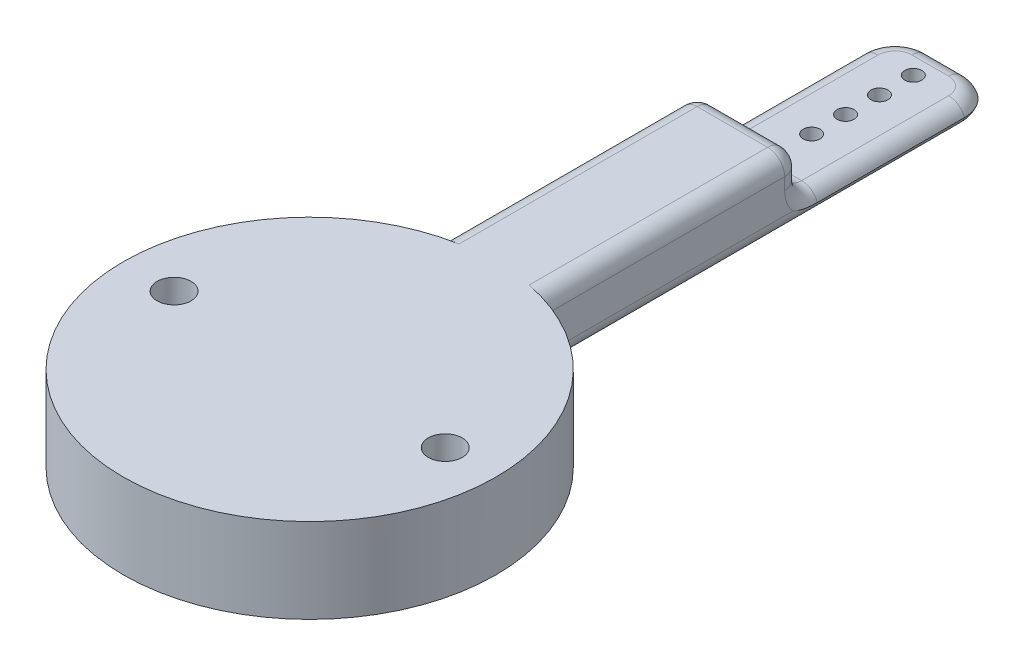
SolidWorks part; units mm, degrees
ref_plane "前视基准面" through (0, 0, 0) normal (0, 0, 1) x (1, 0, 0)
ref_plane "上视基准面" through (0, 0, 0) normal (0, 1, 0) x (1, 0, 0)
ref_plane "右视基准面" through (0, 0, 0) normal (1, 0, 0) x (0, 0, -1)
sketch "草图1" plane through (0, 0, 0) normal (0, 1, 0) x (1, 0, 0)
  circle A0 centre (0, 0) radius 15
  dimension "D1" = 30
extrude "凸台-拉伸3" add sketch "草图1" along normal blind 6
sketch "草图2" plane through (0, 0, 0) normal (0, -1, 0) x (1, 0, 0)
  circle A0 centre (0, 0) radius 10
  dimension "D1" = 20
extrude "切除-拉伸1" cut sketch "草图2" against normal blind 2
sketch "草图3" plane through (0, 2, 0) normal (0, -1, 0) x (1, 0, 0)
  line L0 (-19.2837, 0) -> (17.324, 0) construction
  line L1 (-8, 0) -> (8, 0) construction
  circle A0 centre (8, 0) radius 1
  circle A1 centre (-8, 0) radius 1
  dimension "D3" = 2
  dimension "D4" = 2
  dimension "D1" = 8
  dimension "D2" = 16
extrude "切除-拉伸2" cut sketch "草图3" against normal blind 32
sketch "草图4" plane through (0, 2, 0) normal (0, -1, 0) x (1, 0, 0)
  circle A0 centre (0, 0) radius 4
  dimension "D1" = 8
extrude "切除-拉伸3" cut sketch "草图4" against normal blind 2
sketch "草图5" plane through (0, 6, 0) normal (0, 1, 0) x (1, 0, 0)
  line L0 (0, 0) -> (0, 31.4873) construction
  line L1 (1.8873, 14.6141) -> (3.8489, 14.2239)
  line L4 (-1, 14.7015) -> (1, 14.7015)
  line L6 (4.7021, 13.9651) -> (6.5499, 13.1997)
  line L7 (7.3362, 12.7794) -> (8.9992, 11.6683)
  line L8 (9.6884, 11.1026) -> (11.1026, 9.6884)
  line L9 (11.6683, 8.9992) -> (12.7794, 7.3362)
  line L10 (13.1997, 6.5499) -> (13.9651, 4.7021)
  line L11 (14.2239, 3.8489) -> (14.6141, 1.8873)
  line L12 (14.7015, 1) -> (14.7015, -1)
  line L13 (14.6141, -1.8873) -> (14.2239, -3.8489)
  line L14 (13.9651, -4.7021) -> (13.1997, -6.5499)
  line L15 (12.7794, -7.3362) -> (11.6683, -8.9992)
  line L16 (11.1026, -9.6884) -> (9.6884, -11.1026)
  line L17 (8.9992, -11.6683) -> (7.3362, -12.7794)
  line L18 (6.5499, -13.1997) -> (4.7021, -13.9651)
  line L19 (3.8489, -14.2239) -> (1.8873, -14.6141)
  line L20 (1, -14.7015) -> (-1, -14.7015)
  line L21 (-1.8873, -14.6141) -> (-3.8489, -14.2239)
  line L22 (-4.7021, -13.9651) -> (-6.5499, -13.1997)
  line L23 (-7.3362, -12.7794) -> (-8.9992, -11.6683)
  line L24 (-9.6884, -11.1026) -> (-11.1026, -9.6884)
  line L25 (-11.6683, -8.9992) -> (-12.7794, -7.3362)
  line L26 (-13.1997, -6.5499) -> (-13.9651, -4.7021)
  line L27 (-14.2239, -3.8489) -> (-14.6141, -1.8873)
  line L28 (-14.7015, -1) -> (-14.7015, 1)
  line L29 (-14.6141, 1.8873) -> (-14.2239, 3.8489)
  line L30 (-13.9651, 4.7021) -> (-13.1997, 6.5499)
  line L31 (-12.7794, 7.3362) -> (-11.6683, 8.9992)
  line L32 (-11.1026, 9.6884) -> (-9.6884, 11.1026)
  line L33 (-8.9992, 11.6683) -> (-7.3362, 12.7794)
  line L34 (-6.5499, 13.1997) -> (-4.7021, 13.9651)
  line L35 (-3.8489, 14.2239) -> (-1.8873, 14.6141)
  spline S0 degree 2 poles (0, 17.0015) (-0.7779, 15.9692) (-1, 14.7015) knots 0 0 0 1 1 1
  spline S1 degree 2 poles (0, 17.0015) (0.7445, 15.9556) (1, 14.7015) knots 0 0 0 1 1 1
  spline S2 degree 2 poles (3.3168, 16.6748) (2.3525, 15.8141) (1.8873, 14.6141) knots 0 0 0 1 1 1
  spline S3 degree 2 poles (3.3168, 16.6748) (3.843, 15.5038) (3.8489, 14.2239) knots 0 0 0 1 1 1
  spline S4 degree 2 poles (6.5062, 15.7073) (5.3925, 15.0513) (4.7021, 13.9651) knots 0 0 0 1 1 1
  spline S5 degree 2 poles (6.5062, 15.7073) (6.7938, 14.4561) (6.5499, 13.1997) knots 0 0 0 1 1 1
  spline S6 degree 2 poles (9.4455, 14.1362) (8.2252, 13.7101) (7.3362, 12.7794) knots 0 0 0 1 1 1
  spline S7 degree 2 poles (9.4455, 14.1362) (9.4835, 12.8529) (8.9992, 11.6683) knots 0 0 0 1 1 1
  spline S8 degree 2 poles (12.0219, 12.0219) (10.7419, 11.842) (9.6884, 11.1026) knots 0 0 0 1 1 1
  spline S9 degree 2 poles (12.0219, 12.0219) (11.8088, 10.7558) (11.1026, 9.6884) knots 0 0 0 1 1 1
  spline S10 degree 2 poles (14.1362, 9.4455) (12.8457, 9.5188) (11.6683, 8.9992) knots 0 0 0 1 1 1
  spline S11 degree 2 poles (14.1362, 9.4455) (13.6802, 8.2454) (12.7794, 7.3362) knots 0 0 0 1 1 1
  spline S12 degree 2 poles (15.7073, 6.5062) (14.456, 6.8299) (13.1997, 6.5499) knots 0 0 0 1 1 1
  spline S13 degree 2 poles (15.7073, 6.5062) (15.026, 5.4181) (13.9651, 4.7021) knots 0 0 0 1 1 1
  spline S14 degree 2 poles (16.6748, 3.3168) (15.5106, 3.8784) (14.2239, 3.8489) knots 0 0 0 1 1 1
  spline S15 degree 2 poles (16.6748, 3.3168) (15.7943, 2.3826) (14.6141, 1.8873) knots 0 0 0 1 1 1
  spline S16 degree 2 poles (17.0015, 0) (15.9692, 0.7779) (14.7015, 1) knots 0 0 0 1 1 1
  spline S17 degree 2 poles (17.0015, 0) (15.9556, -0.7445) (14.7015, -1) knots 0 0 0 1 1 1
  spline S18 degree 2 poles (16.6748, -3.3168) (15.8141, -2.3525) (14.6141, -1.8873) knots 0 0 0 1 1 1
  spline S19 degree 2 poles (16.6748, -3.3168) (15.5038, -3.843) (14.2239, -3.8489) knots 0 0 0 1 1 1
  spline S20 degree 2 poles (15.7073, -6.5062) (15.0513, -5.3925) (13.9651, -4.7021) knots 0 0 0 1 1 1
  spline S21 degree 2 poles (15.7073, -6.5062) (14.4561, -6.7938) (13.1997, -6.5499) knots 0 0 0 1 1 1
  spline S22 degree 2 poles (14.1362, -9.4455) (13.7101, -8.2252) (12.7794, -7.3362) knots 0 0 0 1 1 1
  spline S23 degree 2 poles (14.1362, -9.4455) (12.8529, -9.4835) (11.6683, -8.9992) knots 0 0 0 1 1 1
  spline S24 degree 2 poles (12.0219, -12.0219) (11.842, -10.7419) (11.1026, -9.6884) knots 0 0 0 1 1 1
  spline S25 degree 2 poles (12.0219, -12.0219) (10.7558, -11.8088) (9.6884, -11.1026) knots 0 0 0 1 1 1
  spline S26 degree 2 poles (9.4455, -14.1362) (9.5188, -12.8457) (8.9992, -11.6683) knots 0 0 0 1 1 1
  spline S27 degree 2 poles (9.4455, -14.1362) (8.2454, -13.6802) (7.3362, -12.7794) knots 0 0 0 1 1 1
  spline S28 degree 2 poles (6.5062, -15.7073) (6.8299, -14.456) (6.5499, -13.1997) knots 0 0 0 1 1 1
  spline S29 degree 2 poles (6.5062, -15.7073) (5.4181, -15.026) (4.7021, -13.9651) knots 0 0 0 1 1 1
  spline S30 degree 2 poles (3.3168, -16.6748) (3.8784, -15.5106) (3.8489, -14.2239) knots 0 0 0 1 1 1
  spline S31 degree 2 poles (3.3168, -16.6748) (2.3826, -15.7943) (1.8873, -14.6141) knots 0 0 0 1 1 1
  spline S32 degree 2 poles (0, -17.0015) (0.7779, -15.9692) (1, -14.7015) knots 0 0 0 1 1 1
  spline S33 degree 2 poles (0, -17.0015) (-0.7445, -15.9556) (-1, -14.7015) knots 0 0 0 1 1 1
  spline S34 degree 2 poles (-3.3168, -16.6748) (-2.3525, -15.8141) (-1.8873, -14.6141) knots 0 0 0 1 1 1
  spline S35 degree 2 poles (-3.3168, -16.6748) (-3.843, -15.5038) (-3.8489, -14.2239) knots 0 0 0 1 1 1
  spline S36 degree 2 poles (-6.5062, -15.7073) (-5.3925, -15.0513) (-4.7021, -13.9651) knots 0 0 0 1 1 1
  spline S37 degree 2 poles (-6.5062, -15.7073) (-6.7938, -14.4561) (-6.5499, -13.1997) knots 0 0 0 1 1 1
  spline S38 degree 2 poles (-9.4455, -14.1362) (-8.2252, -13.7101) (-7.3362, -12.7794) knots 0 0 0 1 1 1
  spline S39 degree 2 poles (-9.4455, -14.1362) (-9.4835, -12.8529) (-8.9992, -11.6683) knots 0 0 0 1 1 1
  spline S40 degree 2 poles (-12.0219, -12.0219) (-10.7419, -11.842) (-9.6884, -11.1026) knots 0 0 0 1 1 1
  spline S41 degree 2 poles (-12.0219, -12.0219) (-11.8088, -10.7558) (-11.1026, -9.6884) knots 0 0 0 1 1 1
  spline S42 degree 2 poles (-14.1362, -9.4455) (-12.8457, -9.5188) (-11.6683, -8.9992) knots 0 0 0 1 1 1
  spline S43 degree 2 poles (-14.1362, -9.4455) (-13.6802, -8.2454) (-12.7794, -7.3362) knots 0 0 0 1 1 1
  spline S44 degree 2 poles (-15.7073, -6.5062) (-14.456, -6.8299) (-13.1997, -6.5499) knots 0 0 0 1 1 1
  spline S45 degree 2 poles (-15.7073, -6.5062) (-15.026, -5.4181) (-13.9651, -4.7021) knots 0 0 0 1 1 1
  spline S46 degree 2 poles (-16.6748, -3.3168) (-15.5106, -3.8784) (-14.2239, -3.8489) knots 0 0 0 1 1 1
  spline S47 degree 2 poles (-16.6748, -3.3168) (-15.7943, -2.3826) (-14.6141, -1.8873) knots 0 0 0 1 1 1
  spline S48 degree 2 poles (-17.0015, 0) (-15.9692, -0.7779) (-14.7015, -1) knots 0 0 0 1 1 1
  spline S49 degree 2 poles (-17.0015, 0) (-15.9556, 0.7445) (-14.7015, 1) knots 0 0 0 1 1 1
  spline S50 degree 2 poles (-16.6748, 3.3168) (-15.8141, 2.3525) (-14.6141, 1.8873) knots 0 0 0 1 1 1
  spline S51 degree 2 poles (-16.6748, 3.3168) (-15.5038, 3.843) (-14.2239, 3.8489) knots 0 0 0 1 1 1
  spline S52 degree 2 poles (-15.7073, 6.5062) (-15.0513, 5.3925) (-13.9651, 4.7021) knots 0 0 0 1 1 1
  spline S53 degree 2 poles (-15.7073, 6.5062) (-14.4561, 6.7938) (-13.1997, 6.5499) knots 0 0 0 1 1 1
  spline S54 degree 2 poles (-14.1362, 9.4455) (-13.7101, 8.2252) (-12.7794, 7.3362) knots 0 0 0 1 1 1
  spline S55 degree 2 poles (-14.1362, 9.4455) (-12.8529, 9.4835) (-11.6683, 8.9992) knots 0 0 0 1 1 1
  spline S56 degree 2 poles (-12.0219, 12.0219) (-11.842, 10.7419) (-11.1026, 9.6884) knots 0 0 0 1 1 1
  spline S57 degree 2 poles (-12.0219, 12.0219) (-10.7558, 11.8088) (-9.6884, 11.1026) knots 0 0 0 1 1 1
  spline S58 degree 2 poles (-9.4455, 14.1362) (-9.5188, 12.8457) (-8.9992, 11.6683) knots 0 0 0 1 1 1
  spline S59 degree 2 poles (-9.4455, 14.1362) (-8.2454, 13.6802) (-7.3362, 12.7794) knots 0 0 0 1 1 1
  spline S60 degree 2 poles (-6.5062, 15.7073) (-6.8299, 14.456) (-6.5499, 13.1997) knots 0 0 0 1 1 1
  spline S61 degree 2 poles (-6.5062, 15.7073) (-5.4181, 15.026) (-4.7021, 13.9651) knots 0 0 0 1 1 1
  spline S62 degree 2 poles (-3.3168, 16.6748) (-3.8784, 15.5106) (-3.8489, 14.2239) knots 0 0 0 1 1 1
  spline S63 degree 2 poles (-3.3168, 16.6748) (-2.3826, 15.7943) (-1.8873, 14.6141) knots 0 0 0 1 1 1
  point P165 (0, 0)
  dimension "D1" = 32
extrude "凸台-拉伸4" add sketch "草图5" against normal blind 6
sketch "草图6" plane through (0, 6, 0) normal (0, 1, 0) x (1, 0, 0)
  circle A0 centre (0, 0) radius 11
  circle A1 centre (0, 0) radius 17.9461
  dimension "D1" = 22
extrude "切除-拉伸4" cut sketch "草图6" against normal blind 10
sketch "草图7" plane through (0, 0, 0) normal (1, 0, 0) x (0, 0, -1)
  line L0 (11, 6) -> (-11, 6) construction
  line L1 (-12.6632, 6) -> (12.9137, 6)
  line L2 (-12.6632, 6) -> (-12.6632, 5)
  line L3 (-12.6632, 5) -> (12.9137, 5)
  line L4 (12.9137, 6) -> (12.9137, 5)
  dimension "D1" = 1
extrude "切除-拉伸6" cut sketch "草图7" against normal mid plane 30
sketch "草图8" plane through (0, 5, 0) normal (0, 1, 0) x (1, 0, 0)
  line L0 (0, 21.2069) -> (0, 11) construction
  line L1 (0, -2.7734) -> (0, -24.7927) construction
  line L2 (-0.9975, 37.5346) -> (1.1656, 37.5346)
  line L3 (-2.9975, 35.5346) -> (-2.9975, 10.5837)
  line L5 (3.1656, 35.5346) -> (3.1656, 10.5346)
  arc A0 (1.1656, 37.5346) -> (3.1656, 35.5346) centre (1.1656, 35.5346) cw
  arc A1 (-0.9975, 37.5346) -> (-2.9975, 35.5346) centre (-0.9975, 35.5346) ccw
  arc A2 (3.1656, 10.5346) -> (-2.9975, 10.5837) centre (0, 0) ccw
  dimension "D2" = 2
  dimension "D1" = 25
extrude "凸台-拉伸5" add sketch "草图8" against normal blind 4
sketch "草图16" plane through (0, 5, 0) normal (0, 1, 0) x (1, 0, 0)
  line L0 (0.084, 29.1703) -> (0.084, -13.037) construction
  line L1 (1.1656, 37.5346) -> (-0.9975, 37.5346) construction
  circle A0 centre (0.084, 35.5346) radius 0.5
  circle A1 centre (0.084, 33.5346) radius 0.5
  circle A2 centre (0.084, 31.5346) radius 0.5
  circle A3 centre (0.084, 29.5346) radius 0.5
  dimension "D2" = 1
  dimension "D4" = 1
  dimension "D6" = 1
  dimension "D8" = 1
  dimension "D1" = 2
  dimension "D3" = 2
  dimension "D5" = 2
  dimension "D7" = 2
extrude "切除-拉伸11" cut sketch "草图16" against normal blind 11.5
sketch "草图17" plane through (-2.9975, 0, 0) normal (-1, 0, 0) x (0, 0, 1)
  line L0 (-25.8583, 5) -> (-25.8583, 2.3)
  line L1 (-25.8583, 5) -> (-37.9832, 5)
  line L3 (-25.8583, 2.3) -> (-37.9832, 2.3)
  line L4 (-37.9832, 5) -> (-37.9832, 2.3)
  dimension "D1" = 2.7
extrude "切除-拉伸12" cut sketch "草图17" against normal blind 20
fillet "圆角1" radius 1 16 edges at (0.084, 2.3, -37.5346) (-2.4117, 2.3, -36.9489) (2.5798, 2.3, -36.9489) (-2.9975, 2.3, -30.6965) (3.1656, 2.3, -30.6965) (2.5798, 1, -36.9489) (0.084, 1, -37.5346) (-2.4117, 1, -36.9489) (0.084, 5, -25.8583) (-2.9975, 3.65, -25.8583) (0.084, 2.3, -25.8583) (3.1656, 3.65, -25.8583) (3.1656, 1, -23.0346) (-2.9975, 1, -23.0592) (3.1656, 5, -18.1965) (-2.9975, 5, -18.221)
